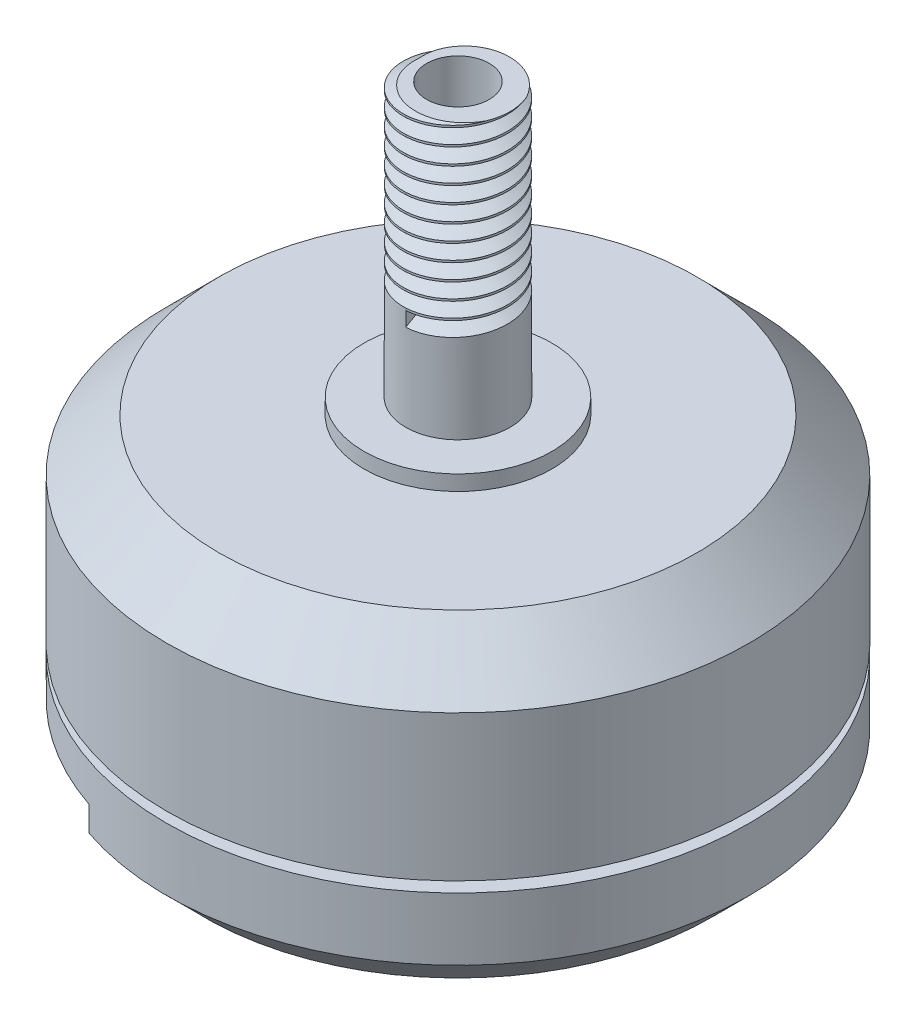
SolidWorks part; units mm, degrees
note: '?' marks a value the reader was unsure of.
ref_plane "Front Plane" through (0, 0, 0) normal (0, 0, 1) x (1, 0, 0)
ref_plane "Top Plane" through (0, 0, 0) normal (0, 1, 0) x (1, 0, 0)
ref_plane "Right Plane" through (0, 0, 0) normal (1, 0, 0) x (0, 0, -1)
sketch "Sketch1" plane through (0, 0, 0) normal (0, 1, 0) x (1, 0, 0)
  circle A0 centre (0, 0) radius 13.95
  dimension "D1" = 27.9
extrude "Boss-Extrude1" add sketch "Sketch1" along normal blind 4.8
sketch "Sketch2" plane through (0, 4.8, 0) normal (0, 1, 0) x (1, 0, 0)
  circle A0 centre (0, 0) radius 5
  dimension "D1" = 10
extrude "Boss-Extrude2" add sketch "Sketch2" along normal blind 0.5
sketch "Sketch3" plane through (0, 5.3, 0) normal (0, 1, 0) x (1, 0, 0)
  circle A1 centre (0, 0) radius 13.95
  circle A2 centre (0, 0) radius 13.95
  dimension "D1" = 0
extrude "Boss-Extrude3" add sketch "Sketch3" along normal offset from surface (9.47 mm away) 14.77 separate body up to face at (0, 0, 13.95)
sketch "Sketch4" plane through (0, 14.77, 0) normal (0, 1, 0) x (1, 0, 0)
  circle A0 centre (0, 0) radius 4.5
  dimension "D1" = 9
extrude "Boss-Extrude4" add sketch "Sketch4" along normal offset from surface (0.73 mm away) 15.5 separate body up to face at (0, 0, 13.95)
sketch "Sketch5" plane through (0, 15.5, 0) normal (0, 1, 0) x (1, 0, 0)
  circle A0 centre (0, 0) radius 2.5
  dimension "D1" = 5
extrude "Boss-Extrude5" add sketch "Sketch5" along normal blind 13.1
sketch "Sketch6" plane through (0, 28.6, 0) normal (0, 1, 0) x (1, 0, 0)
  circle A0 centre (0, 0) radius 1.5
  dimension "D1" = 3
extrude "Cut-Extrude1" cut sketch "Sketch6" against normal up to surface (13.83 mm away) up to face at (0, 14.77, 13.95)
ref_axis "Axis1" through (0, 28.6, 0) along (0, -1, 0)?
sketch "Sketch7" plane through (0, 28.6, 0) normal (0, 1, 0) x (1, 0, 0)
  circle A0 centre (0, 0) radius 2.5 construction
  circle A1 centre (0, 0) radius 2.5
curve "Helix/Spiral1" pitch 0.8 height 8.6 turns 10.75
ref_plane "Plane1" through (0, 0, 0) normal (0, 0, -1) x (-1, 0, 0)
sketch "Sketch8" plane through (0, 0, 0) normal (0, 0, -1) x (-1, 0, 0)
  line L0 (2.5, 28.95) -> (2.5, 28.25)
  line L1 (2.5, 28.25) -> (1.8938, 28.6)
  line L2 (1.8938, 28.6) -> (2.5, 28.95)
  point P2 (2.5, 28.6)
  dimension "D1" = 0.7
sweep "Cut-Sweep1" cut profiles "Sketch8" path "Helix/Spiral1" align with end faces yes
sketch "Sketch9" plane through (0, 0, 0) normal (0, -1, 0) x (1, 0, 0)
  line L0 (0, 8) -> (0, 0) construction
  line L1 (0, 0) -> (0, -8) construction
  line L2 (0, 0) -> (9.5, 0) construction
  line L3 (0, 0) -> (-9.5, 0) construction
  circle A0 centre (0, 8) radius 1.5
  circle A1 centre (0, -8) radius 1.5
  circle A2 centre (9.5, 0) radius 1.5
  circle A3 centre (-9.5, 0) radius 1.5
  dimension "D1" = 3
  dimension "D2" = 19
  dimension "D3" = 16
extrude "Cut-Extrude2" cut sketch "Sketch9" against normal blind 2.7
sketch "Sketch10" plane through (0, 0, 0) normal (0, -1, 0) x (1, 0, 0)
  line L0 (-13.2212, 4.45) -> (-6.6481, 4.45)
  line L1 (-11, 0) -> (-13.95, 0) construction
  line L2 (-4.45, 6.6481) -> (-4.45, 13.2212)
  line L3 (-9.5, 1.5) -> (-9.5, 4.45) construction
  circle A0 centre (0, 0) radius 13.95 construction
  arc A1 (-6.6481, 4.45) -> (-4.45, 6.6481) centre (0, 0) cw
  circle A2 centre (-9.5, 0) radius 1.5 construction
  arc A3 (-13.2212, 4.45) -> (-4.45, 13.2212) centre (0, 0) cw
  circle M9 centre (0, 0) radius 13.95
extrude "Cut-Extrude3" cut sketch "Sketch10" against normal blind 3 contours L0 A1 L2 M9
sketch "Sketch11" plane through (0, 0, 0) normal (0, -1, 0) x (1, 0, 0)
  circle A0 centre (0, 0) radius 4
  dimension "D1" = 8
extrude "Boss-Extrude6" add sketch "Sketch11" along normal blind 0.5 separate body
sketch "Sketch12" plane through (0, -0.5, 0) normal (0, -1, 0) x (1, 0, 0)
  circle A0 centre (0, 0) radius 2
  dimension "D1" = 4
extrude "Boss-Extrude7" add sketch "Sketch12" along normal blind 2
fillet "Fillet1" radius 2 1 edges at (0, -2.5, -2)
chamfer "Chamfer1" distance 1.8 angle 45 1 edges at (9.8641, 0, -9.8641)
chamfer "Chamfer2" distance 2.5 angle 45 1 edges at (0, 14.77, 13.95)
ref_plane "Plane2" through (0, 12.27, 0) normal (0, 1, 0) x (1, 0, 0)
ref_axis "Axis2" through (9.5, 2.7, 0) along (0, -1, 0)?
ref_axis "Axis3" through (-9.5, 2.7, 0) along (0, -1, 0)?
ref_plane "Plane3" through (0, 0, 0) normal (0, 0, 1) x (1, 0, 0)
equation "\"D1@Boss-Extrude7\"=\"D1@Sketch12\"/2"
equation "\"D1@Fillet1\"=\"D1@Boss-Extrude7\""
